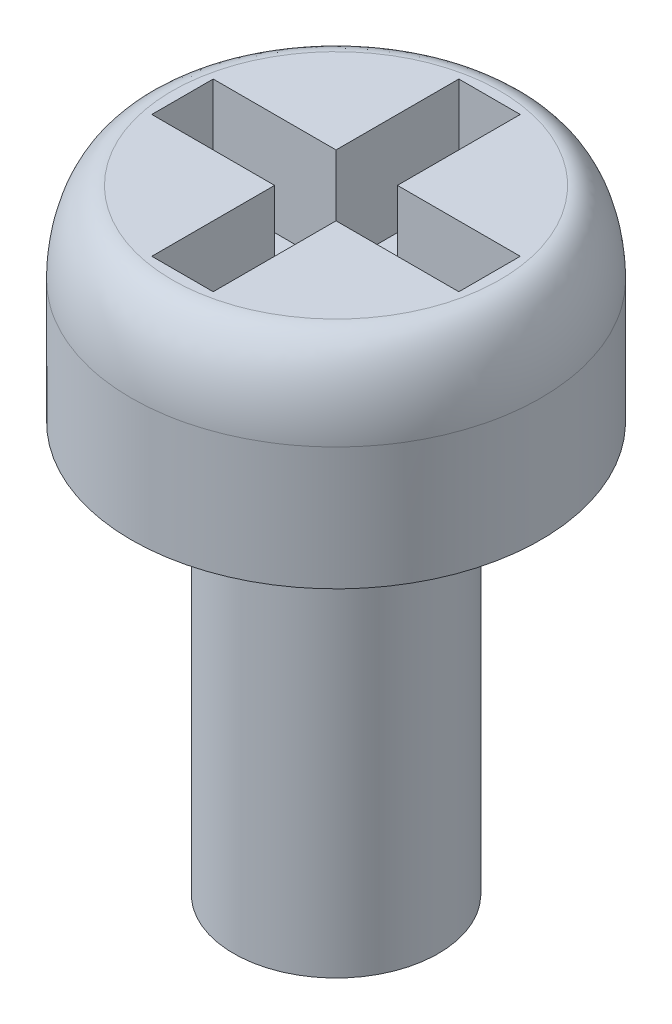
SolidWorks part; units mm, degrees
ref_plane "Front Plane" through (0, 0, 0) normal (0, 0, 1) x (1, 0, 0)
ref_plane "Top Plane" through (0, 0, 0) normal (0, 1, 0) x (1, 0, 0)
ref_plane "Right Plane" through (0, 0, 0) normal (1, 0, 0) x (0, 0, -1)
sketch "Sketch1" plane through (0, 0, 0) normal (0, 1, 0) x (1, 0, 0)
  circle A0 centre (0, 0) radius 3
  dimension "D1" = 6
extrude "Boss-Extrude1" add sketch "Sketch1" along normal blind 3
sketch "Sketch2" plane through (0, 0, 0) normal (0, -1, 0) x (1, 0, 0)
  circle A0 centre (0, 0) radius 1.5
  dimension "D1" = 3
extrude "Boss-Extrude2" add sketch "Sketch2" along normal blind 6
sketch "Sketch3" plane through (0, 3, 0) normal (0, 1, 0) x (1, 0, 0)
  line L0 (-0.45, 2.25) -> (-0.45, 0.45)
  line L1 (-0.45, 2.25) -> (0.45, 2.25)
  line L3 (-0.45, -2.25) -> (0.45, -2.25)
  line L5 (0, -2.25) -> (0, 2.25) construction
  line L6 (-0.45, 0) -> (0.45, 0) construction
  line L8 (-2.25, 0.45) -> (-2.25, -0.45)
  line L10 (2.25, 0.45) -> (2.25, -0.45)
  line L11 (0, -0.45) -> (0, 0.45) construction
  line L12 (-2.25, 0) -> (2.25, 0) construction
  line L13 (-0.45, -2.25) -> (-0.45, -0.45)
  line L14 (0.45, 2.25) -> (0.45, 0.45)
  line L15 (0.45, -2.25) -> (0.45, -0.45)
  line L16 (-2.25, -0.45) -> (-0.45, -0.45)
  line L17 (0.45, -0.45) -> (2.25, -0.45)
  line L18 (-2.25, 0.45) -> (-0.45, 0.45)
  line L19 (0.45, 0.45) -> (2.25, 0.45)
  point P0 (0, 0)
  point P4 (0, 0)
  dimension "D1" = 0.9
  dimension "D2" = 4.5
  dimension "D3" = 0.9
  dimension "D4" = 4.5
extrude "Cut-Extrude1" cut sketch "Sketch3" against normal blind 1.5
fillet "Fillet1" radius 1.2 1 edges at (0, 3, 3) second distance 0.6 first distance on face at (0, 3, 3)
